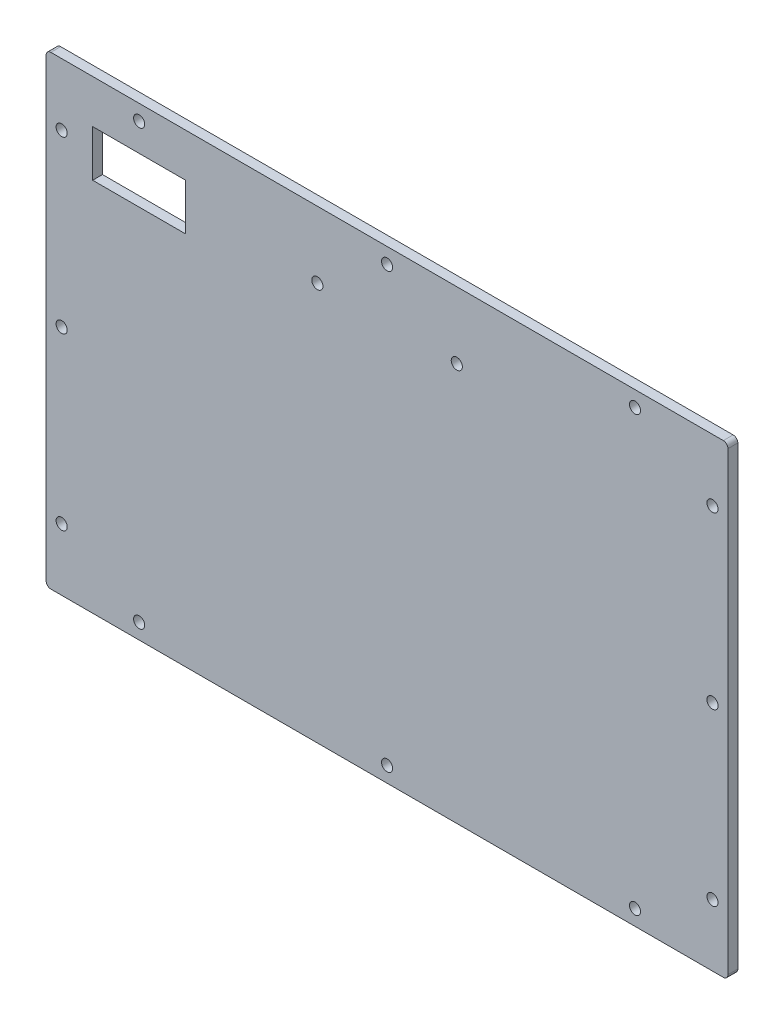
SolidWorks part; units mm, degrees
ref_plane "Front Plane" through (0, 0, 0) normal (0, 0, 1) x (1, 0, 0)
ref_plane "Top Plane" through (0, 0, 0) normal (0, 1, 0) x (1, 0, 0)
ref_plane "Right Plane" through (0, 0, 0) normal (1, 0, 0) x (0, 0, -1)
sketch "Sketch1" plane through (0, 0, 0) normal (0, 0, 1) x (1, 0, 0)
  line L0 (0, 0) -> (0, 75) construction
  line L1 (-110, -75) -> (110, -75)
  line L2 (-110, -75) -> (-110, 75)
  line L3 (-110, 75) -> (110, 75)
  line L4 (110, -75) -> (110, 75)
  line L5 (-110, -75) -> (110, 75) construction
  line L6 (-110, 75) -> (110, -75) construction
  line L15 (0, 0) -> (-110, 0) construction
  point P0 (0, 0)
  dimension "D1" = 220
  dimension "D2" = 150
extrude "Boss-Extrude1" add sketch "Sketch1" along normal blind 3.175 contours L3 L2 L1 L4 region at (0, 0, 0)
hole_wizard "M3 Clearance Hole1" positions "Sketch2" profile "Sketch3" hole size "M3" standard "ANSI Metric" end condition through all
sketch "Sketch2" plane through (0, 0, 3.175) normal (0, 0, 1) x (1, 0, 0)
  line L1 (-105, -70) -> (105, -70)
  line L2 (-105, -70) -> (-105, 70)
  line L3 (-105, 70) -> (105, 70)
  line L4 (105, -70) -> (105, 70)
  line L5 (-105, -70) -> (105, 70) construction
  line L6 (-105, 70) -> (105, -70) construction
  line L7 (-110, -75) -> (-110, 75) construction
  line L8 (-110, 75) -> (110, 75) construction
  point P2 (0, 0)
  point P113 (-80, 70)
  point P115 (80, 70)
  point P116 (0, 70)
  point P118 (-105, 55)
  point P120 (-105, 0)
  point P122 (-105, -55)
  point P124 (-80, -70)
  point P126 (0, -70)
  point P128 (80, -70)
  point P130 (105, -55)
  point P132 (105, 0)
  point P134 (105, 55)
  dimension "D1" = 5
  dimension "D2" = 5
  dimension "D3" = 80
  dimension "D4" = 80
  dimension "D5" = 55
  dimension "D6" = 55
sketch "Sketch3" plane through (0, 0, 3.175) normal (1, 0, 0) x (0, -1, 0)
  line L0 (0, 0) -> (0, 3.175)
  line L1 (0, 3.175) -> (1.8, 3.175)
  line L2 (1.8, 3.175) -> (1.8, 0)
  line L5 (1.8, 0) -> (0, 0)
  line L11 (0, -6.35) -> (0, 107.95) construction
  dimension "Thru Hole Dia." = 3.6
  dimension "Thru Hole Depth" = 3.175
sketch "Sketch4" plane through (0, 0, 3.175) normal (0, 0, 1) x (1, 0, 0)
  line L1 (-5, -5) -> (5, -5)
  line L2 (-5, -5) -> (-5, 5)
  line L3 (-5, 5) -> (5, 5)
  line L4 (5, -5) -> (5, 5)
  line L5 (-5, -5) -> (5, 5) construction
  line L6 (-5, 5) -> (5, -5) construction
  point P0 (0, 0)
  dimension "D1" = 10
  dimension "D2" = 10
extrude "Boss-Extrude2" add sketch "Sketch4" against normal through all
fillet "Fillet2" radius 1.5 4 edges at (-110, -75, 1.5875) (110, -75, 1.5875) (110, 75, 1.5875) (-110, 75, 1.5875)
sketch "Sketch7" plane through (0, 0, 3.175) normal (0, 0, 1) x (1, 0, 0)
  line L8 (-100, -65) -> (100, -65)
  line L9 (-100, 65) -> (-100, -65)
  line L10 (100, 65) -> (-100, 65)
  line L11 (100, -65) -> (100, 65)
  line L12 (-100, -65) -> (100, -65) construction
  line L13 (-100, 65) -> (-100, -65) construction
  line L14 (100, 65) -> (-100, 65) construction
  line L15 (100, -65) -> (100, 65) construction
  line L20 (-22.5, 53.5) -> (22.5, 53.5) construction
  line L22 (-49.5, 42) -> (49.5, 42) construction
  line L23 (-49.5, 42) -> (-49.5, 65) construction
  line L24 (-49.5, 65) -> (49.5, 65) construction
  line L25 (49.5, 42) -> (49.5, 65) construction
  line L26 (-49.5, 42) -> (49.5, 65) construction
  line L27 (-49.5, 65) -> (49.5, 42) construction
  line L29 (-95, 46) -> (-65, 46)
  line L30 (-95, 46) -> (-95, 61)
  line L31 (-95, 61) -> (-65, 61)
  line L32 (-65, 46) -> (-65, 61)
  line L33 (-95, 46) -> (-65, 61) construction
  line L34 (-95, 61) -> (-65, 46) construction
  point P0 (-96.4541, -46.1324)
  point P1 (0, 65)
  point P66 (-22.5, 53.5)
  point P67 (22.5, 53.5)
  point P76 (0, 53.5)
  point P138 (-80, 53.5)
  dimension "D2" = 45
  dimension "D3" = 99
  dimension "D4" = 23
  dimension "D5" = 15
  dimension "D6" = 30
  dimension "D7" = 5
  dimension "D1" = 10
extrude "Cut-Extrude2" cut sketch "Sketch7" against normal through all
hole_wizard "M3 Clearance Hole3" positions "Sketch8" profile "Sketch9" hole size "M3" standard "ANSI Metric" end condition through all
sketch "Sketch8" plane through (0, 0, 3.175) normal (0, 0, 1) x (1, 0, 0)
  point P0 (-22.5, 53.5)
  point P3 (22.5, 53.5)
sketch "Sketch9" plane through (-22.5, 53.5, 3.175) normal (1, 0, 0) x (0, -1, 0)
  line L0 (0, 0) -> (0, 3.175)
  line L1 (0, 3.175) -> (1.8, 3.175)
  line L2 (1.8, 3.175) -> (1.8, 0)
  line L5 (1.8, 0) -> (0, 0)
  line L11 (0, -6.35) -> (0, 107.95) construction
  dimension "Thru Hole Dia." = 3.6
  dimension "Thru Hole Depth" = 3.175
